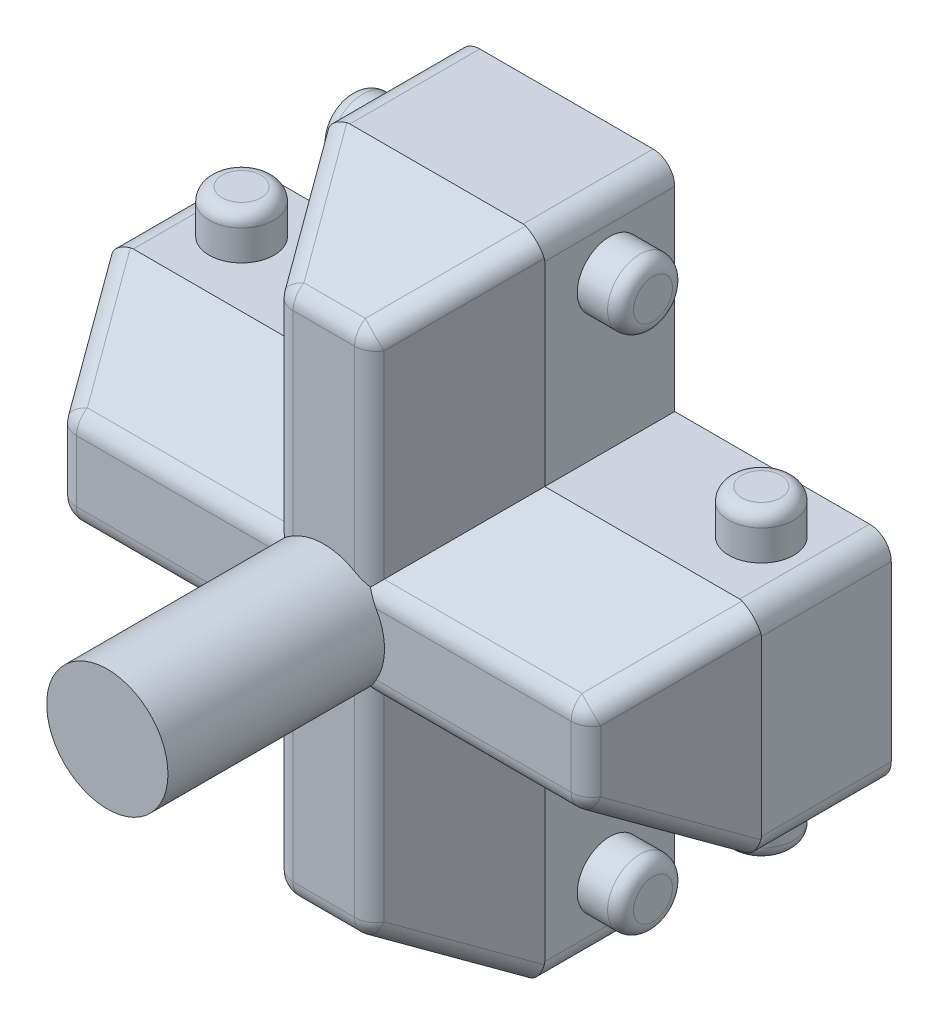
SolidWorks part; units mm, degrees
ref_plane "Front Plane" through (0, 0, 0) normal (0, 0, 1) x (1, 0, 0)
ref_plane "Top Plane" through (0, 0, 0) normal (0, 1, 0) x (1, 0, 0)
ref_plane "Right Plane" through (0, 0, 0) normal (1, 0, 0) x (0, 0, -1)
sketch "Sketch2" plane through (0, 0, 0) normal (0, 0, 1) x (1, 0, 0)
  circle A0 centre (0, 0) radius 14
  dimension "D1" = 28
extrude "Boss-Extrude1" add sketch "Sketch2" along normal blind 76
sketch "Sketch3" plane through (0, 0, 0) normal (0, 0, -1) x (-1, 0, 0)
  line L1 (75, 25) -> (-75, 25)
  line L2 (75, 25) -> (75, -25)
  line L3 (75, -25) -> (-75, -25)
  line L4 (-75, 25) -> (-75, -25)
  line L5 (75, 25) -> (-75, -25) construction
  line L6 (75, -25) -> (-75, 25) construction
  line L7 (25, -75) -> (-25, -75)
  line L8 (25, -75) -> (25, 75)
  line L9 (25, 75) -> (-25, 75)
  line L10 (-25, -75) -> (-25, 75)
  line L11 (25, -75) -> (-25, 75) construction
  line L12 (25, 75) -> (-25, -75) construction
  point P0 (0, 0)
  point P6 (0, 0)
  circle M9 centre (0, 0) radius 14
  dimension "D1" = 150
  dimension "D2" = 150
  dimension "D3" = 50
  dimension "D4" = 50
extrude "Boss-Extrude2" add sketch "Sketch3" along normal blind 30 contours L3 L10 L1 L4 | L10 L1 L8 L9 | L8 L3 L2 L1 | L10 L7 L8 L3 | L10 L3 L8 L1 M9 | M9 region at (-50, 0, 0) region at (-24.2929, 0, 0) region at (0, 50, 0) region at (50, 0, 0) region at (0, -50, 0) region at (0, 0, 0)
ref_plane "Plane1" through (0, 0, 0) normal (1, 0, 0) x (0, 0, -1)
sketch "Sketch5" plane through (0, 0, 0) normal (1, 0, 0) x (0, 0, -1)
  line L0 (15, 75) -> (15, 25) construction
  line L1 (30, 75) -> (0, 75) construction
  line L2 (30, 25) -> (0, 25) construction
  line L3 (0, 0) -> (30, 0) construction
  line L4 (30, 25) -> (30, -25) construction
  circle A0 centre (15, 60) radius 7.5
  circle A1 centre (15, -60) radius 7.5
  dimension "D1" = 15
  dimension "D2" = 15
extrude "Boss-Extrude3" add sketch "Sketch5" along normal mid plane 70
sketch "Sketch6" plane through (0, 0, 0) normal (0, 1, 0) x (1, 0, 0)
  line L0 (-75, 15) -> (75, 15) construction
  line L1 (-75, 30) -> (-75, 0) construction
  line L2 (75, 30) -> (75, 0) construction
  line L3 (0, 0) -> (0, 29.4662) construction
  line L4 (0, -16.5) -> (0, 16.5) construction
  circle A0 centre (-60, 15) radius 7.5
  circle A1 centre (60, 15) radius 7.5
  dimension "D2" = 15
  dimension "D1" = 15
extrude "Boss-Extrude4" add sketch "Sketch6" along normal mid plane 70
sketch "Sketch7" plane through (0, 0, 0) normal (0, 0, 1) x (1, 0, 0)
  line L12 (25, -25) -> (75, -25)
  line L13 (75, -25) -> (75, 25)
  line L14 (75, 25) -> (25, 25)
  line L15 (25, 25) -> (25, 75)
  line L16 (25, 75) -> (-25, 75)
  line L17 (-25, 75) -> (-25, 25)
  line L18 (-25, 25) -> (-75, 25)
  line L19 (-75, 25) -> (-75, -25)
  line L20 (-75, -25) -> (-25, -25)
  line L21 (-25, -25) -> (-25, -75)
  line L22 (-25, -75) -> (25, -75)
  line L23 (25, -75) -> (25, -25)
  line L24 (25, -25) -> (75, -25)
  line L25 (75, -25) -> (75, 25)
  line L26 (75, 25) -> (25, 25)
  line L27 (25, 25) -> (25, 75)
  line L28 (25, 75) -> (-25, 75)
  line L29 (-25, 75) -> (-25, 25)
  line L30 (-25, 25) -> (-75, 25)
  line L31 (-75, 25) -> (-75, -25)
  line L32 (-75, -25) -> (-25, -25)
  line L33 (-25, -25) -> (-25, -75)
  line L34 (-25, -75) -> (25, -75)
  line L35 (25, -75) -> (25, -25)
  dimension "D1" = 0
extrude "Boss-Extrude5" add sketch "Sketch7" along normal blind 26 draft 30
fillet "Fillet2" radius 5 28 edges at (-75, 25, -15) (-75, -25, -15) (-25, -75, -15) (25, -75, -15) (75, -25, -15) (75, 25, -15) (-25, 75, -15) (25, 75, -15) (-67.4944, 17.4944, 13) (-67.4944, -17.4944, 13) (-17.4944, -67.4944, 13) (17.4944, -67.4944, 13) (67.4944, -17.4944, 13) (67.4944, 17.4944, 13) (17.4944, 67.4944, 13) (-17.4944, 67.4944, 13) (0, -59.9889, 26) (-9.9889, -34.9889, 26) (-34.9889, -9.9889, 26) (-59.9889, 0, 26) (-34.9889, 9.9889, 26) (-9.9889, 34.9889, 26) (34.9889, 9.9889, 26) (59.9889, 0, 26) (34.9889, -9.9889, 26) (9.9889, -34.9889, 26) (0, 59.9889, 26) (9.9889, 34.9889, 26)
fillet "Fillet3" radius 3 8 edges at (-35, -60, -7.5) (35, -60, -7.5) (-60, -35, -7.5) (60, -35, -22.5) (60, 35, -22.5) (-60, 35, -7.5) (35, 60, -22.5) (-35, 60, -22.5)
